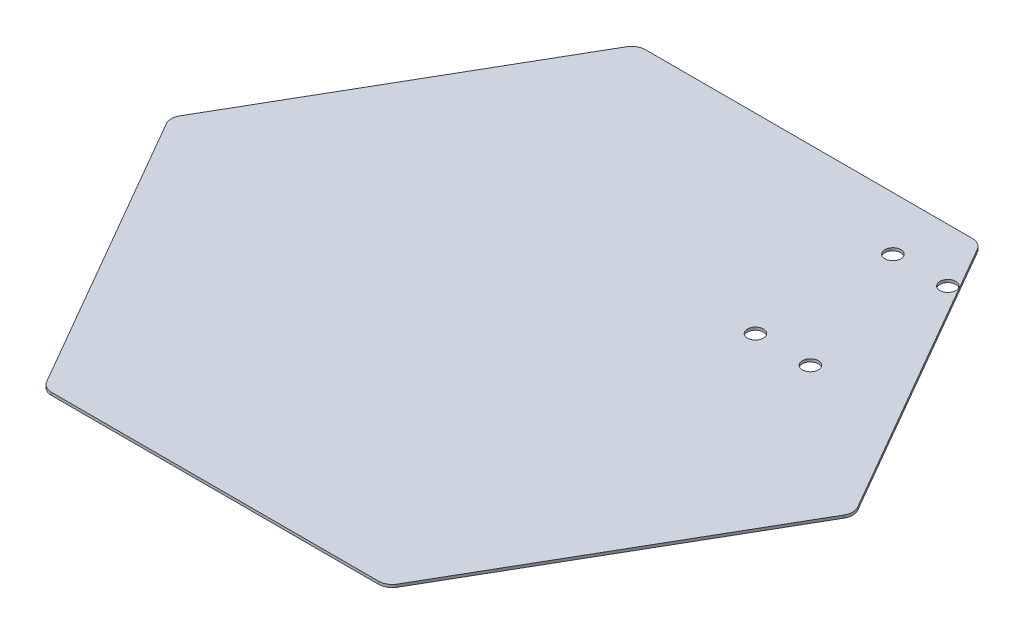
SolidWorks part; units mm, degrees
material "Thornel Mat VMA"
ref_plane "Front Plane" through (0, 0, 0) normal (0, 0, 1) x (1, 0, 0)
ref_plane "Top Plane" through (0, 0, 0) normal (0, 1, 0) x (1, 0, 0)
ref_plane "Right Plane" through (0, 0, 0) normal (1, 0, 0) x (0, 0, -1)
sketch "Sketch1" plane through (0, 0, 0) normal (0, 1, 0) x (1, 0, 0)
  line L1 (62.3538, 0) -> (187.0615, 0)
  line L2 (187.0615, 0) -> (249.4153, 108)
  line L3 (249.4153, 108) -> (187.0615, 216)
  line L4 (187.0615, 216) -> (62.3538, 216)
  line L5 (62.3538, 216) -> (0, 108)
  line L6 (0, 108) -> (62.3538, 0)
  circle A0 centre (124.7077, 108) radius 108 construction
  dimension "D1" = 216
extrude "Boss-Extrude1" add sketch "Sketch1" along normal blind 1
fillet "Fillet1" radius 5 6 edges at (0, 0.5, -108) (62.3538, 0.5, -216) (187.0615, 0.5, -216) (249.4153, 0.5, -108) (62.3538, 0.5, 0) (187.0615, 0.5, 0)
sketch "Sketch2" plane through (0, 1, 0) normal (0, 1, 0) x (1, 0, 0)
  line L0 (124.7077, 0) -> (124.7077, 216) construction
  line L1 (65.2406, 0) -> (184.1747, 0) construction
  line L2 (184.1747, 216) -> (65.2406, 216) construction
  line L3 (124.7077, 108) -> (253.6879, 108) construction
  line L4 (174.7077, 196.57) -> (194.7077, 196.57)
  line L5 (174.7077, 196.57) -> (174.7077, 146.57)
  line L6 (174.7077, 146.57) -> (194.7077, 146.57)
  line L7 (194.7077, 196.57) -> (194.7077, 146.57)
  line L8 (174.7077, 196.57) -> (194.7077, 146.57) construction
  line L9 (174.7077, 146.57) -> (194.7077, 196.57) construction
  point P6 (184.7077, 171.57)
  dimension "D1" = 50
  dimension "D2" = 20
  dimension "D3" = 50
  dimension "D4" = 38.57
hole_wizard "M5 Clearance Hole1" positions "Sketch4" profile "Sketch5" hole size "M5" standard "ANSI Metric"
sketch "Sketch4" plane through (0, 1, 0) normal (0, 1, 0) x (1, 0, 0)
  point P0 (174.7077, 146.57)
  point P3 (194.7077, 146.57)
  point P6 (194.7077, 196.57)
  point P9 (174.7077, 196.57)
sketch "Sketch5" plane through (174.7077, 1, -146.57) normal (1, 0, 0) x (0, 0, 1)
  line L0 (0, 0) -> (0, 6.7425)
  line L1 (0, 6.7425) -> (2.9, 5)
  line L2 (2.9, 5) -> (2.9, 0)
  line L5 (2.9, 0) -> (0, 0)
  line L10 (0, 6.7425) -> (-2.9, 5) construction
  line L11 (0, -6.35) -> (0, 107.95) construction
  dimension "Hole Dia." = 5.8
  dimension "Hole Depth" = 5
  dimension "Drill Angle" = 118
